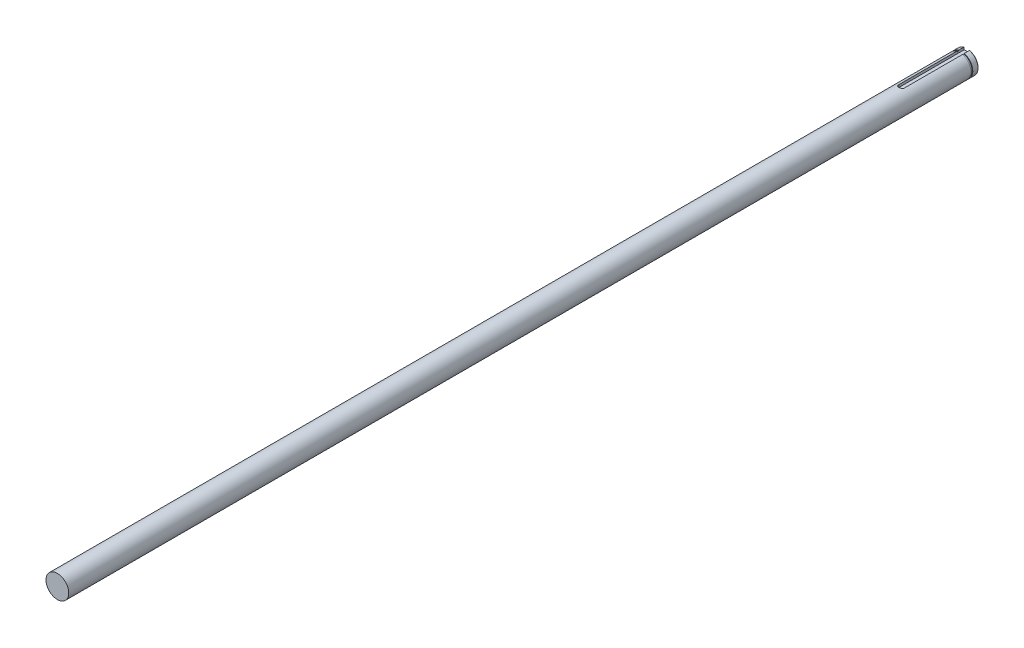
SolidWorks part; units mm, degrees
material "AISI 4130 Steel, normalized at 870C"
ref_plane "Front Plane" through (0, 0, 0) normal (0, 0, 1) x (1, 0, 0)
ref_plane "Top Plane" through (0, 0, 0) normal (0, 1, 0) x (1, 0, 0)
ref_plane "Right Plane" through (0, 0, 0) normal (1, 0, 0) x (0, 0, -1)
sketch "Sketch1" plane through (0, 0, 0) normal (0, 0, 1) x (1, 0, 0)
  circle A0 centre (0, 0) radius 6.35
  dimension "D1" = 12.7
extrude "Boss-Extrude1" add sketch "Sketch1" along normal blind 508
sketch "Sketch2" plane through (0, 0, 0) normal (0, 0, -1) x (-1, 0, 0)
  line L1 (-1.5875, 4.7625) -> (1.5875, 4.7625)
  line L2 (-1.5875, 4.7625) -> (-1.5875, 7.9375)
  line L3 (-1.5875, 7.9375) -> (1.5875, 7.9375)
  line L4 (1.5875, 4.7625) -> (1.5875, 7.9375)
  line L5 (-1.5875, 4.7625) -> (1.5875, 7.9375) construction
  line L6 (-1.5875, 7.9375) -> (1.5875, 4.7625) construction
  circle A0 centre (0, 0) radius 6.35 construction
  point P0 (0, 6.35)
  dimension "D1" = 3.175
  dimension "D2" = 3.175
extrude "Cut-Extrude1" cut sketch "Sketch2" against normal blind 38.1
ref_plane "Plane1" through (0, 0, 3.175) normal (0, 0, -1) x (-1, 0, 0)
sketch "Sketch3" plane through (0, 0, 3.175) normal (0, 0, -1) x (-1, 0, 0)
  circle A0 centre (0, 0) radius 5.9436
  circle A1 centre (0, 0) radius 9.1947
  dimension "D1" = 11.8872
extrude "Cut-Extrude2" cut sketch "Sketch3" against normal blind 0.9906
chamfer "Chamfer1" distance 0.254 angle 45 1 edges at (0, -6.35, 0)
fillet "Fillet1" radius 1.5875 2 edges at (-1.5875, 5.4554, 38.1) (1.5875, 5.4554, 38.1)
